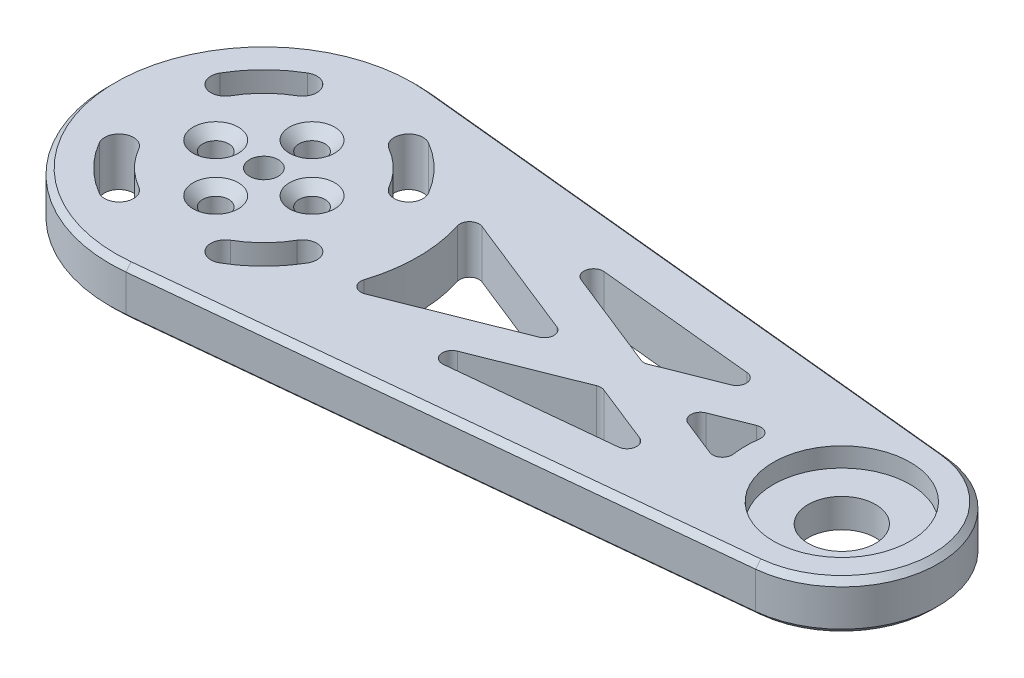
SolidWorks part; units mm, degrees
material "三聚氰胺甲醛树脂"
ref_plane "前视基准面" through (0, 0, 0) normal (0, 0, 1) x (1, 0, 0)
ref_plane "上视基准面" through (0, 0, 0) normal (0, 1, 0) x (1, 0, 0)
ref_plane "右视基准面" through (0, 0, 0) normal (1, 0, 0) x (0, 0, -1)
sketch "草图1" plane through (0, 0, 0) normal (0, 1, 0) x (1, 0, 0)
  line L0 (0, 0) -> (-5.9584, 0) construction
  line L1 (1.6, -15.9198) -> (61, -9.9499)
  line L2 (1.6, 15.9198) -> (61, 9.9499)
  line L3 (19.8889, 9.0565) -> (47.5675, 6.2747)
  line L4 (19.8889, -9.0565) -> (47.5675, -6.2747)
  line L5 (12.6607, 9.783) -> (51.8832, -5.841) construction
  line L6 (12.6607, -9.783) -> (51.8832, 5.841) construction
  line L7 (14.4221, 6.9285) -> (31.8155, 0)
  line L8 (19.8889, 9.0565) -> (37.22, 2.1528)
  line L9 (14.4221, -6.9285) -> (31.8155, 0)
  line L10 (19.8889, -9.0565) -> (37.22, -2.1528)
  line L11 (37.22, 2.1528) -> (47.5675, 6.2747)
  line L12 (42.6245, 0) -> (50.5056, -3.1394)
  line L13 (42.6245, 0) -> (50.5056, 3.1394)
  line L14 (37.22, -2.1528) -> (47.5675, -6.2747)
  line L15 (7.7782, -7.7782) -> (0, 0) construction
  circle A0 centre (0, 0) radius 5 construction
  circle A1 centre (-5, 0) radius 1.35
  circle A2 centre (0, 5) radius 1.35
  circle A3 centre (5, 0) radius 1.35
  circle A4 centre (0, -5) radius 1.35
  arc A5 (1.6, 15.9198) -> (1.6, -15.9198) centre (0, 0) ccw
  circle A6 centre (0, 0) radius 1.5
  arc A7 (50.5056, 3.1394) -> (50.5056, -3.1394) centre (60, 0) ccw
  circle A8 centre (60, 0) radius 3.5
  circle A9 centre (60, 0) radius 7.1
  arc A10 (14.4221, -6.9285) -> (14.4221, 6.9285) centre (0, 0) ccw
  circle A11 centre (0, 0) radius 16 construction
  arc A12 (61, -9.9499) -> (61, 9.9499) centre (60, 0) ccw
  circle A13 centre (60, 0) radius 10 construction
  arc A14 (5.5166, -9.5166) -> (9.5166, -5.5166) centre (0, 0) ccw construction
  arc A15 (6.2689, -10.8144) -> (10.8144, -6.2689) centre (0, 0) ccw
  arc A16 (4.7644, -8.2189) -> (8.2189, -4.7644) centre (0, 0) ccw
  arc A17 (4.7644, -8.2189) -> (6.2689, -10.8144) centre (5.5166, -9.5166) ccw
  arc A18 (10.8144, -6.2689) -> (8.2189, -4.7644) centre (9.5166, -5.5166) ccw
  arc A19 (-9.5166, -5.5166) -> (-5.5166, -9.5166) centre (0, 0) ccw construction
  arc A20 (-10.8144, -6.2689) -> (-6.2689, -10.8144) centre (0, 0) ccw
  arc A21 (-8.2189, -4.7644) -> (-4.7644, -8.2189) centre (0, 0) ccw
  arc A22 (-8.2189, -4.7644) -> (-10.8144, -6.2689) centre (-9.5166, -5.5166) ccw
  arc A23 (-6.2689, -10.8144) -> (-4.7644, -8.2189) centre (-5.5166, -9.5166) ccw
  arc A24 (-5.5166, 9.5166) -> (-9.5166, 5.5166) centre (0, 0) ccw construction
  arc A25 (-6.2689, 10.8144) -> (-10.8144, 6.2689) centre (0, 0) ccw
  arc A26 (-4.7644, 8.2189) -> (-8.2189, 4.7644) centre (0, 0) ccw
  arc A27 (-4.7644, 8.2189) -> (-6.2689, 10.8144) centre (-5.5166, 9.5166) ccw
  arc A28 (-10.8144, 6.2689) -> (-8.2189, 4.7644) centre (-9.5166, 5.5166) ccw
  arc A29 (9.5166, 5.5166) -> (5.5166, 9.5166) centre (0, 0) ccw construction
  arc A30 (10.8144, 6.2689) -> (6.2689, 10.8144) centre (0, 0) ccw
  arc A31 (8.2189, 4.7644) -> (4.7644, 8.2189) centre (0, 0) ccw
  arc A32 (8.2189, 4.7644) -> (10.8144, 6.2689) centre (9.5166, 5.5166) ccw
  arc A33 (6.2689, 10.8144) -> (4.7644, 8.2189) centre (5.5166, 9.5166) ccw
  point P15 (0, 0)
  point P36 (7.7782, -7.7782)
  point P53 (-7.7782, -7.7782)
  point P60 (-7.7782, 7.7782)
  point P67 (7.7782, 7.7782)
  point P72 (0, 0)
  dimension "D1" = 10
  dimension "D2" = 2.7
  dimension "D4" = 20
  dimension "D5" = 32
  dimension "D6" = 3
  dimension "D7" = 7
  dimension "D8" = 14.2
  dimension "D15" = 11
  dimension "D16" = 1.5
  dimension "D3" = 60
  dimension "D9" = 5
  dimension "D10" = 5
  dimension "D11" = 2
  dimension "D12" = 2
  dimension "D13" = 2
  dimension "D14" = 2
  dimension "D17" = 4
  dimension "D18" = 45
  dimension "D19" = 4
extrude "凸台-拉伸1" add sketch "草图1" along normal blind 5 contours L1 A7 L2 A5 A9 A1 A2 A3 A4 A6 region at (-15.0824, 0, 0)
extrude "凸台-拉伸2" add sketch "草图1<3>" along normal blind 3 contours A9 A8 region at (53.1008, 0, 0)
sketch "草图1<3>" plane through (0, 0, 0) normal (0, 1, 0) x (1, 0, 0) same geometry as "草图1"
fillet "圆角1" radius 1 12 edges at (42.6245, 2.5, 0) (50.5056, 2.5, -3.1394) (50.5056, 2.5, 3.1394) (47.5675, 2.5, -6.2747) (19.8889, 2.5, -9.0565) (37.22, 2.5, -2.1528) (31.8155, 2.5, 0) (14.4221, 2.5, -6.9285) (14.4221, 2.5, 6.9285) (19.8889, 2.5, 9.0565) (37.22, 2.5, 2.1528) (47.5675, 2.5, 6.2747)
sketch "草图2" plane through (0, 5, 0) normal (0, 1, 0) x (1, 0, 0)
  line L0 (1.35, -13.4323) -> (60.75, -7.4624)
  line L1 (60.75, 7.4624) -> (1.35, 13.4323)
  line L2 (1.6, -15.9198) -> (61, -9.9499)
  line L3 (61, 9.9499) -> (1.6, 15.9198)
  line L4 (1.6, -15.9198) -> (61, -9.9499)
  line L5 (61, 9.9499) -> (1.6, 15.9198)
  arc A0 (1.35, 13.4323) -> (1.35, -13.4323) centre (0, 0) ccw
  arc A1 (60.75, -7.4624) -> (60.75, 7.4624) centre (60, 0) ccw
  arc A2 (61, -9.9499) -> (61, 9.9499) centre (60, 0) ccw
  arc A3 (1.6, 15.9198) -> (1.6, -15.9198) centre (0, 0) ccw
  arc A4 (61, -9.9499) -> (61, 9.9499) centre (60, 0) ccw
  arc A5 (1.6, 15.9198) -> (1.6, -15.9198) centre (0, 0) ccw
  dimension "D1" = 0
  dimension "D2" = 2.5
chamfer "倒角1" distance 0.6 angle 45 8 edges at (31.3, 5, 12.9348) (-16, 5, 0) (70, 5, 0) (31.3, 5, -12.9348) (31.3, 0, 12.9348) (-16, 0, 0) (70, 0, 0) (31.3, 0, -12.9348)
chamfer "倒角2" distance 1 angle 45 4 edges at (-5, 5, 1.35) (0, 5, 6.35) (5, 5, 1.35) (0, 5, -3.65)
